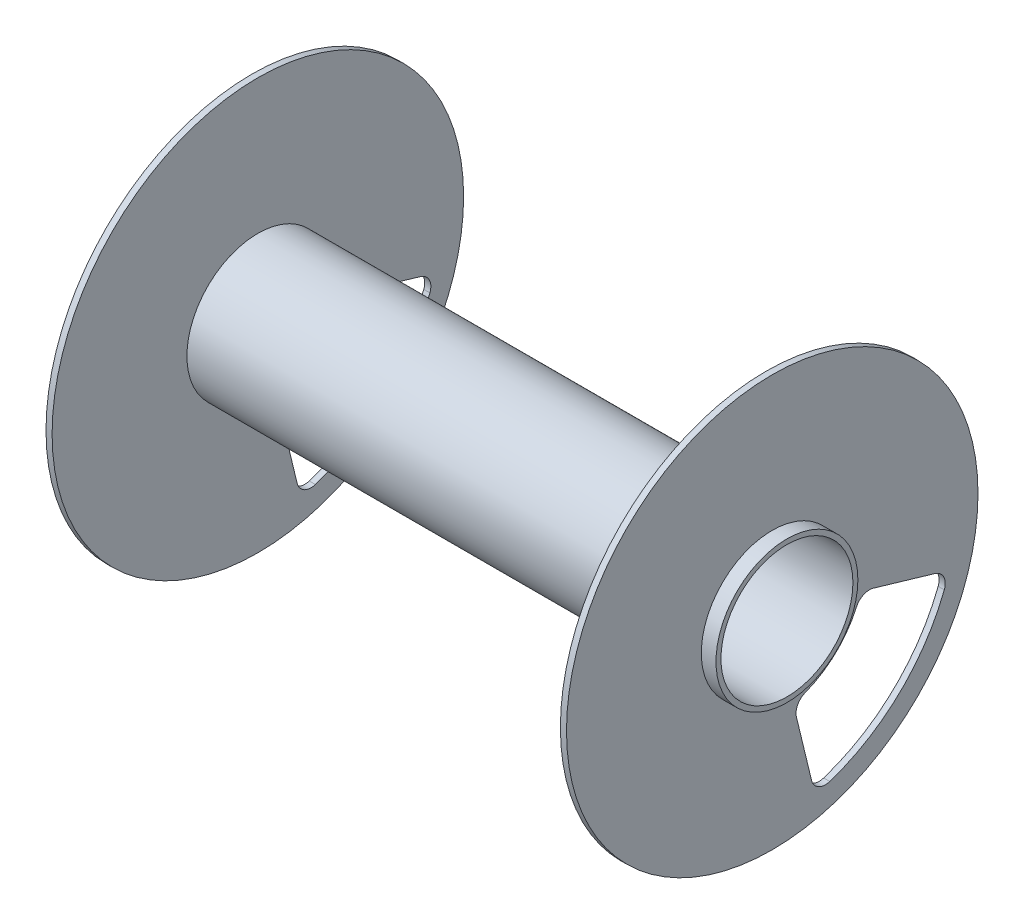
SolidWorks part; units mm, degrees
ref_plane "Front Plane" through (0, 0, 0) normal (0, 0, 1) x (1, 0, 0)
ref_plane "Top Plane" through (0, 0, 0) normal (0, 1, 0) x (1, 0, 0)
ref_plane "Right Plane" through (0, 0, 0) normal (1, 0, 0) x (0, 0, -1)
ref_axis "Axis1" through (50.6845, 0, 0) along (-1, 0, 0)
sketch "Sketch2" plane through (0, 0, 0) normal (0, 0, 1) x (1, 0, 0)
  line L0 (-52.3875, 11.811) -> (-52.3875, 12.7)
  line L1 (26.9176, 11.811) -> (49.2125, 11.811)
  line L2 (-52.3875, 12.7) -> (-46.5836, 12.7)
  line L3 (-46.5836, 12.7) -> (-46.5836, 36.83)
  line L4 (-46.5836, 36.83) -> (-45.4914, 36.83)
  line L5 (-45.4914, 36.83) -> (-45.4914, 12.7)
  line L6 (-45.4914, 12.7) -> (45.4914, 12.7)
  line L7 (45.4914, 12.7) -> (45.4914, 36.83)
  line L8 (45.4914, 36.83) -> (46.5836, 36.83)
  line L9 (46.5836, 36.83) -> (46.5836, 12.7)
  line L10 (46.5836, 12.7) -> (49.2125, 12.7)
  line L11 (49.2125, 12.7) -> (49.2125, 11.811)
  line L14 (50.6845, 0) -> (-56.1784, 0) construction
  line L15 (0, 0) -> (-94.3879, 0) construction
  line L16 (-52.3875, 11.811) -> (20.7073, 11.811)
  line L17 (20.7073, 11.811) -> (20.7073, 9.3663)
  line L18 (20.7073, 9.3663) -> (26.9176, 9.3663)
  line L19 (26.9176, 9.3663) -> (26.9176, 11.811)
  point P14 (46.0375, 36.83)
  point P17 (-46.0375, 36.83)
  point P23 (23.8125, 9.3663)
  point P26 (0, 12.7)
  dimension "D1" = 25.4
  dimension "D2" = 23.622
  dimension "D3" = 101.6
  dimension "D4" = 1.0922
  dimension "D5" = 98.425
  dimension "D6" = 6.35
  dimension "D7" = 73.66
  dimension "D8" = 18.7325
  dimension "D9" = 25.4
  dimension "D10" = 6.2103
revolve "Revolve1" add sketch "Sketch2" angle 360 about L15
sketch "Sketch3" plane through (45.4914, 0, 0) normal (-1, 0, 0) x (0, 0, 1)
  line L0 (-18.113, -5.3265) -> (-29.1401, -8.5693)
  line L1 (-4.3279, -18.3942) -> (-7.0317, -29.5594)
  circle A2 centre (0, 0) radius 33.02
  arc A3 (-30.7921, -11.9233) -> (-10.292, -31.3751) centre (0, 0) ccw
  arc A4 (-5.8903, -15.4235) -> (-4.3279, -18.3942) centre (-6.7965, -17.7964) cw
  circle A5 centre (0, 0) radius 16.51
  arc A6 (-15.0768, -6.7282) -> (-5.8903, -15.4235) centre (0, 0) ccw
  arc A7 (-10.292, -31.3751) -> (-7.0317, -29.5594) centre (-9.5003, -28.9616) ccw
  arc A8 (-30.7921, -11.9233) -> (-29.1401, -8.5693) centre (-28.4235, -11.0061) cw
  arc A9 (-18.113, -5.3265) -> (-15.0768, -6.7282) centre (-17.3964, -7.7633) cw
  dimension "D4" = 2.54
  dimension "D3" = 60
  dimension "D1" = 3.81
  dimension "D2" = 3.81
extrude "Cut-Extrude1" cut sketch "Sketch3" against normal through all and the other way through all
